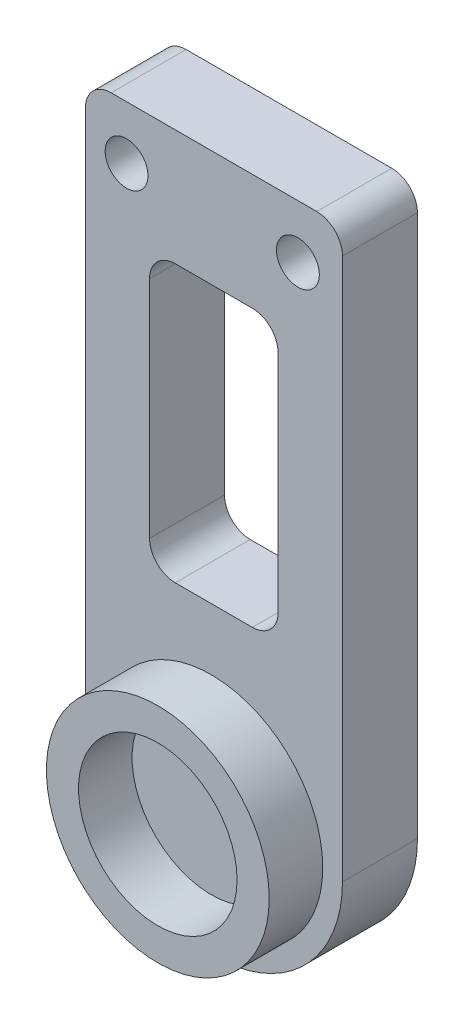
SolidWorks part; units mm, degrees
ref_plane "Front Plane" through (0, 0, 0) normal (0, 0, 1) x (1, 0, 0)
ref_plane "Top Plane" through (0, 0, 0) normal (0, 1, 0) x (1, 0, 0)
ref_plane "Right Plane" through (0, 0, 0) normal (1, 0, 0) x (0, 0, -1)
other "Graphic1"
ref_plane "Plane1" through (0, 0, 10) normal (0, 0, 1) x (1, 0, 0)
sketch "Sketch1" plane through (0, 0, 10) normal (0, 0, 1) x (1, 0, 0)
  line L1 (-282.9889, 283.3511) -> (-270.9889, 283.3511)
  line L2 (-282.9889, 283.3511) -> (-282.9889, 250.8511)
  line L3 (-282.9889, 250.8511) -> (-270.9889, 250.8511)
  line L4 (-270.9889, 283.3511) -> (-270.9889, 250.8511)
  line L5 (-279.9945, 277.9372) -> (-273.9945, 277.9372)
  line L6 (-279.9945, 277.9372) -> (-279.9945, 265.0372)
  line L7 (-279.9945, 265.0372) -> (-273.9945, 265.0372)
  line L8 (-273.9945, 277.9372) -> (-273.9945, 265.0372)
  circle A0 centre (-281.0692, 280.8544) radius 1
  circle A1 centre (-273.0692, 280.8544) radius 1
  dimension "D3" = 8
  dimension "D1" = 12
  dimension "D2" = 32.5
  dimension "D4" = 6
  dimension "D5" = 12.9
extrude "Boss-Extrude1" add sketch "Sketch1" along normal blind 3.5
fillet "Fillet1" radius 1.2 6 edges at (-279.9945, 265.0372, 11.75) (-273.9945, 265.0372, 11.75) (-273.9945, 277.9372, 11.75) (-279.9945, 277.9372, 11.75) (-282.9889, 283.3511, 11.75) (-270.9889, 283.3511, 11.75)
fillet "Fillet2" radius 6 2 edges at (-282.9889, 250.8511, 11.75) (-270.9889, 250.8511, 11.75)
sketch "Sketch2" plane through (0, 0, 13.5) normal (0, 0, 1) x (1, 0, 0)
  circle A0 centre (-277.1102, 256.964) radius 3.7
  circle A1 centre (-277.1102, 256.964) radius 5.2
extrude "Boss-Extrude2" add sketch "Sketch2" along normal blind 2.5
